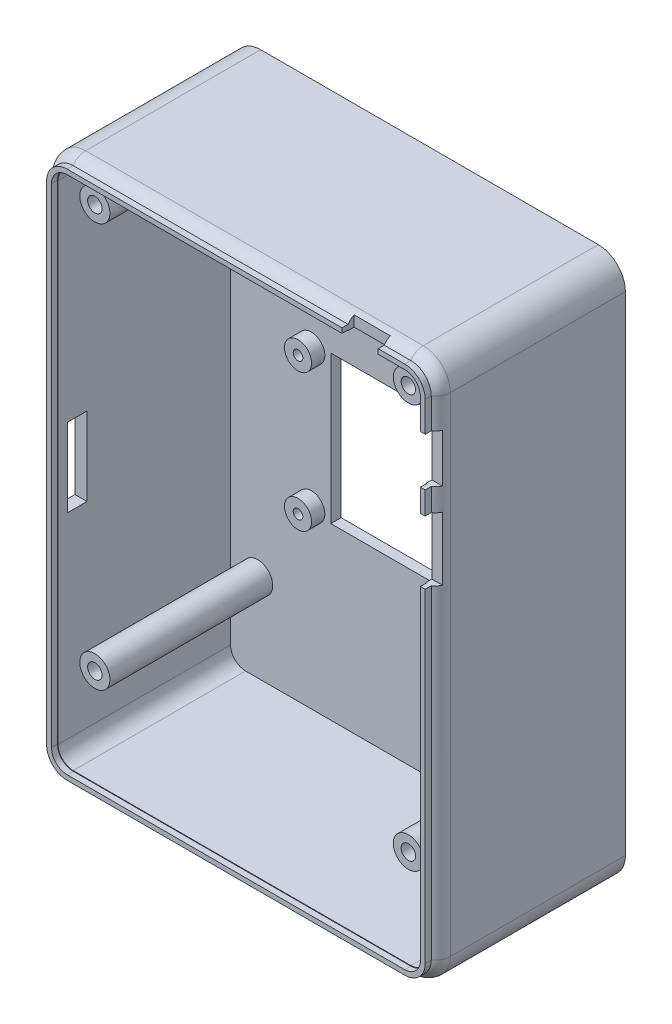
SolidWorks part; units mm, degrees
ref_plane "前基準面" through (0, 0, 0) normal (0, 0, 1) x (1, 0, 0)
ref_plane "上基準面" through (0, 0, 0) normal (0, 1, 0) x (1, 0, 0)
ref_plane "右基準面" through (0, 0, 0) normal (1, 0, 0) x (0, 0, -1)
sketch "草圖1" plane through (0, 0, 0) normal (0, 0, 1) x (1, 0, 0)
  line L0 (2, -87.5) -> (58, -87.5)
  line L1 (62.5, -83) -> (62.5, -2)
  line L2 (58, 2.5) -> (2, 2.5)
  line L3 (-2.5, -2) -> (-2.5, -83)
  arc A0 (58, -87.5) -> (62.5, -83) centre (58, -83) ccw
  arc A1 (62.5, -2) -> (58, 2.5) centre (58, -2) ccw
  arc A2 (2, 2.5) -> (-2.5, -2) centre (2, -2) ccw
  arc A3 (-2.5, -83) -> (2, -87.5) centre (2, -83) ccw
extrude "floor" add sketch "草圖1" along normal blind 2.5
sketch "草圖2" plane through (0, 0, 0) normal (0, 0, 1) x (1, 0, 0)
  line L0 (2, -87.5) -> (58, -87.5)
  line L1 (62.5, -83) -> (62.5, -2)
  line L2 (58, 2.5) -> (2, 2.5)
  line L3 (-2.5, -2) -> (-2.5, -83)
  line L4 (2, -86.5) -> (58, -86.5)
  line L5 (61.5, -83) -> (61.5, -2)
  line L6 (58, 1.5) -> (2, 1.5)
  line L7 (-1.5, -2) -> (-1.5, -83)
  arc A0 (58, -87.5) -> (62.5, -83) centre (58, -83) ccw
  arc A1 (62.5, -2) -> (58, 2.5) centre (58, -2) ccw
  arc A2 (2, 2.5) -> (-2.5, -2) centre (2, -2) ccw
  arc A3 (-2.5, -83) -> (2, -87.5) centre (2, -83) ccw
  arc A4 (58, -86.5) -> (61.5, -83) centre (58, -83) ccw
  arc A5 (61.5, -2) -> (58, 1.5) centre (58, -2) ccw
  arc A6 (2, 1.5) -> (-1.5, -2) centre (2, -2) ccw
  arc A7 (-1.5, -83) -> (2, -86.5) centre (2, -83) ccw
extrude "wall outer half" add sketch "草圖2" along normal blind 31.1
sketch "草圖3" plane through (0, 0, 0) normal (0, 0, 1) x (1, 0, 0)
  line L0 (2, -86.5) -> (58, -86.5)
  line L1 (61.5, -83) -> (61.5, -2)
  line L2 (58, 1.5) -> (2, 1.5)
  line L3 (-1.5, -2) -> (-1.5, -83)
  line L4 (2, -85.5) -> (58, -85.5)
  line L5 (60.5, -83) -> (60.5, -2)
  line L6 (58, 0.5) -> (2, 0.5)
  line L7 (-0.5, -2) -> (-0.5, -83)
  arc A0 (58, -86.5) -> (61.5, -83) centre (58, -83) ccw
  arc A1 (61.5, -2) -> (58, 1.5) centre (58, -2) ccw
  arc A2 (2, 1.5) -> (-1.5, -2) centre (2, -2) ccw
  arc A3 (-1.5, -83) -> (2, -86.5) centre (2, -83) ccw
  arc A4 (58, -85.5) -> (60.5, -83) centre (58, -83) ccw
  arc A5 (60.5, -2) -> (58, 0.5) centre (58, -2) ccw
  arc A6 (2, 0.5) -> (-0.5, -2) centre (2, -2) ccw
  arc A7 (-0.5, -83) -> (2, -85.5) centre (2, -83) ccw
extrude "wall inner half" add sketch "草圖3" along normal blind 31.1
sketch "草圖4" plane through (0, 0, 0) normal (0, 0, 1) x (1, 0, 0)
  line L0 (2, -86.4) -> (58, -86.4)
  line L1 (61.4, -83) -> (61.4, -2)
  line L2 (58, 1.4) -> (2, 1.4)
  line L3 (-1.4, -2) -> (-1.4, -83)
  line L4 (2, -85.6) -> (58, -85.6)
  line L5 (60.6, -83) -> (60.6, -2)
  line L6 (58, 0.6) -> (2, 0.6)
  line L7 (-0.6, -2) -> (-0.6, -83)
  arc A0 (58, -86.4) -> (61.4, -83) centre (58, -83) ccw
  arc A1 (61.4, -2) -> (58, 1.4) centre (58, -2) ccw
  arc A2 (2, 1.4) -> (-1.4, -2) centre (2, -2) ccw
  arc A3 (-1.4, -83) -> (2, -86.4) centre (2, -83) ccw
  arc A4 (58, -85.6) -> (60.6, -83) centre (58, -83) ccw
  arc A5 (60.6, -2) -> (58, 0.6) centre (58, -2) ccw
  arc A6 (2, 0.6) -> (-0.6, -2) centre (2, -2) ccw
  arc A7 (-0.6, -83) -> (2, -85.6) centre (2, -83) ccw
extrude "lip" add sketch "草圖4" along normal blind 32.1
fillet "screen face round-over" radius 2.5 8 edges at (-1.182, -86.182, 31.1) (-2.5, -42.5, 31.1) (-1.182, 1.182, 31.1) (30, 2.5, 31.1) (61.182, 1.182, 31.1) (62.5, -42.5, 31.1) (61.182, -86.182, 31.1) (30, -87.5, 31.1)
sketch "草圖5" plane through (0, 0, 0) normal (0, 0, 1) x (1, 0, 0)
  circle A0 centre (4, -4) radius 2.5
  circle A1 centre (56, -4) radius 2.5
  circle A2 centre (4, -71) radius 2.5
  circle A3 centre (56, -71) radius 2.5
extrude "standoffs" add sketch "草圖5" along normal blind 29.5
sketch "草圖6" plane through (0, 0, 0) normal (0, 0, 1) x (1, 0, 0)
  circle A0 centre (4, -4) radius 1.2
  circle A1 centre (56, -4) radius 1.2
  circle A2 centre (4, -71) radius 1.2
  circle A3 centre (56, -71) radius 1.2
extrude "screw bores" cut sketch "草圖6" along normal through all
sketch "草圖7" plane through (0, 0, 0) normal (0, 0, 1) x (1, 0, 0)
  circle A0 centre (4, -4) radius 2.1
  circle A1 centre (56, -4) radius 2.1
  circle A2 centre (4, -71) radius 2.1
  circle A3 centre (56, -71) radius 2.1
extrude "screw head recesses" cut sketch "草圖7" along normal blind 1.5
sketch "草圖8" plane through (0, 0, 0) normal (0, 0, 1) x (1, 0, 0)
  circle A0 centre (12.9, -33.6) radius 2.25
  circle A1 centre (12.9, -56.4) radius 2.25
  circle A2 centre (47.1, -33.6) radius 2.25
  circle A3 centre (47.1, -56.4) radius 2.25
extrude "display posts" add sketch "草圖8" along normal blind 4.7
sketch "草圖9" plane through (0, 0, 0) normal (0, 0, 1) x (1, 0, 0)
  circle A0 centre (12.9, -33.6) radius 0.8
  circle A1 centre (12.9, -56.4) radius 0.8
  circle A2 centre (47.1, -33.6) radius 0.8
  circle A3 centre (47.1, -56.4) radius 0.8
extrude "display post pilot holes M2" cut sketch "草圖9" against normal blind 4 from offset 4.7
sketch "草圖10" plane through (0, 0, 0) normal (0, 0, 1) x (1, 0, 0)
  line L0 (14.15, -59.25) -> (42.65, -59.25)
  line L1 (42.65, -59.25) -> (42.65, -30.75)
  line L2 (42.65, -30.75) -> (14.15, -30.75)
  line L3 (14.15, -30.75) -> (14.15, -59.25)
extrude "screen frame recess" cut sketch "草圖10" along normal blind 0.8
sketch "草圖11" plane through (0, 0, 0) normal (0, 0, 1) x (1, 0, 0)
  line L0 (16.15, -57.25) -> (40.65, -57.25)
  line L1 (40.65, -57.25) -> (40.65, -32.75)
  line L2 (40.65, -32.75) -> (16.15, -32.75)
  line L3 (16.15, -32.75) -> (16.15, -57.25)
extrude "display window" cut sketch "草圖11" along normal through all
sketch "草圖12" plane through (0, 0, 0) normal (0, 0, 1) x (1, 0, 0)
  circle A0 centre (53, -14) radius 1
extrude "charge LED hole D2" cut sketch "草圖12" along normal through all
sketch "草圖13" plane through (0, 0, 0) normal (1, 0, 0) x (0, 0, -1)
  line L0 (-26.3, -50.5) -> (-29.5, -50.5)
  line L1 (-29.5, -50.5) -> (-29.5, -37.5)
  line L2 (-29.5, -37.5) -> (-26.3, -37.5)
  line L3 (-26.3, -37.5) -> (-26.3, -50.5)
extrude "microSD slot" cut sketch "草圖13" against normal through all
sketch "草圖14" plane through (0, 0, 0) normal (1, 0, 0) x (0, 0, -1)
  line L0 (-30.1, -29.25) -> (-32.6, -29.25)
  line L1 (-32.6, -29.25) -> (-32.6, -18.75)
  line L2 (-32.6, -18.75) -> (-30.1, -18.75)
  line L3 (-30.1, -18.75) -> (-30.1, -29.25)
extrude "USB-C lip notch" cut sketch "草圖14" along normal blind 4.5 from offset 59
sketch "草圖15" plane through (0, 0, 0) normal (1, 0, 0) x (0, 0, -1)
  line L0 (-30.1, -15) -> (-32.6, -15)
  line L1 (-32.6, -15) -> (-32.6, -7)
  line L2 (-32.6, -7) -> (-30.1, -7)
  line L3 (-30.1, -7) -> (-30.1, -15)
extrude "switch lip notch" cut sketch "草圖15" along normal blind 4.5 from offset 59
sketch "草圖16" plane through (0, 0, 0) normal (0, 1, 0) x (1, 0, 0)
  line L0 (47.6, -30.1) -> (53.6, -30.1)
  line L1 (53.6, -30.1) -> (53.6, -32.6)
  line L2 (53.6, -32.6) -> (47.6, -32.6)
  line L3 (47.6, -32.6) -> (47.6, -30.1)
extrude "shutter lip notch" cut sketch "草圖16" along normal through all
